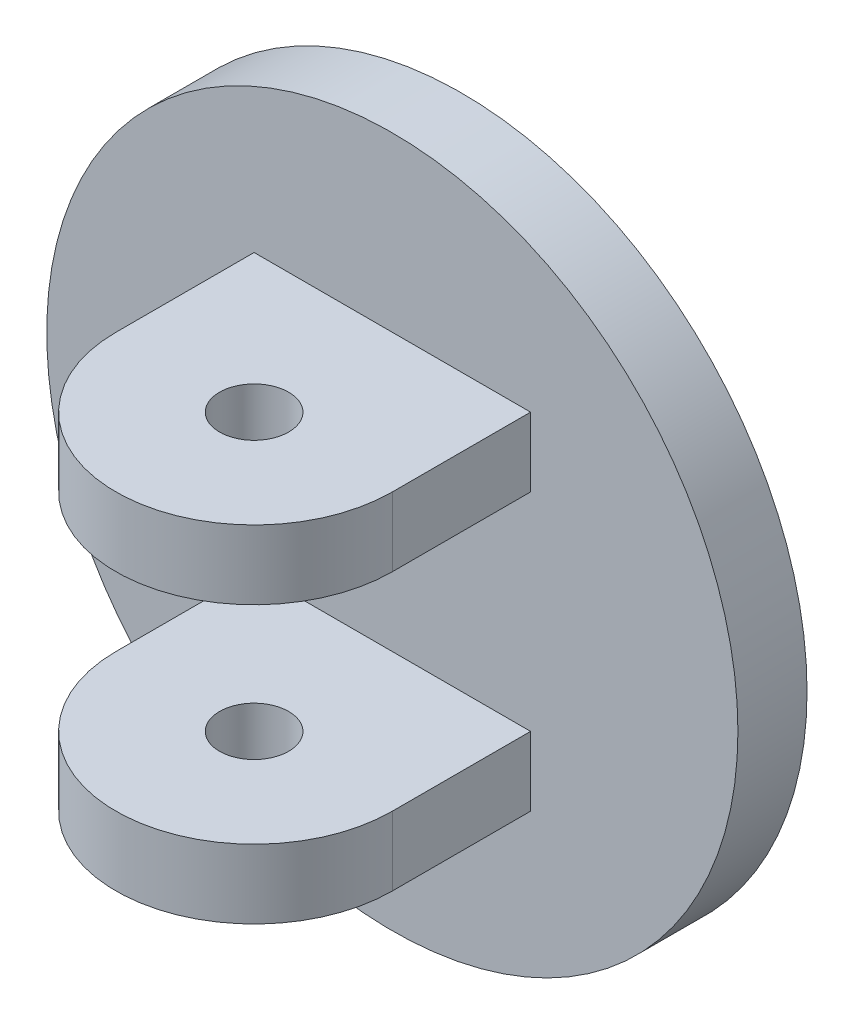
SolidWorks part; units mm, degrees
ref_plane "Front Plane" through (0, 0, 0) normal (0, 0, 1) x (1, 0, 0)
ref_plane "Top Plane" through (0, 0, 0) normal (0, 1, 0) x (1, 0, 0)
ref_plane "Right Plane" through (0, 0, 0) normal (1, 0, 0) x (0, 0, -1)
sketch "Sketch1" plane through (0, 0, 0) normal (0, 0, 1) x (1, 0, 0)
  circle A0 centre (0, 0) radius 50
  dimension "D1" = 100
extrude "Boss-Extrude1" add sketch "Sketch1" along normal blind 10
sketch "Sketch2" plane through (0, 0, 10) normal (0, 0, 1) x (1, 0, 0)
  line L2 (0, 15) -> (20, 15)
  line L4 (0, 25) -> (20, 25)
  line L5 (20, 15) -> (20, 25)
  line L6 (0, 15) -> (-20, 15)
  line L8 (0, 25) -> (-20, 25)
  line L9 (-20, 15) -> (-20, 25)
  line L10 (0, -15) -> (20, -15)
  line L12 (0, -25) -> (20, -25)
  line L13 (20, -15) -> (20, -25)
  line L14 (0, -15) -> (-20, -15)
  line L16 (0, -25) -> (-20, -25)
  line L17 (-20, -15) -> (-20, -25)
  point P4 (0, 0)
  dimension "D1" = 30
  dimension "D2" = 20
  dimension "D3" = 20
  dimension "D4" = 10
  dimension "D5" = 20
  dimension "D6" = 20
  dimension "D7" = 10
extrude "Boss-Extrude2" add sketch "Sketch2" along normal blind 40
sketch "Sketch3" plane through (0, 25, 0) normal (0, 1, 0) x (1, 0, 0)
  circle A0 centre (0, -30) radius 5
  dimension "D1" = 10
extrude "Cut-Extrude1" cut sketch "Sketch3" against normal blind 51 and the other way blind 10
sketch "Sketch4" plane through (0, -25, 0) normal (0, -1, 0) x (1, 0, 0)
  line L0 (20, 50) -> (20, 10) construction
  line L1 (-20, 50) -> (-20, 10) construction
  line L2 (-20, 30) -> (-47.3665, 30)
  line L3 (-47.3665, 30) -> (-38.9642, 74.7454)
  line L4 (-38.9642, 74.7454) -> (40.8393, 70.5722)
  line L5 (40.8393, 70.5722) -> (55.137, 30)
  line L6 (55.137, 30) -> (20, 30)
  arc A0 (20, 30) -> (-20, 30) centre (0, 30) ccw
extrude "Cut-Extrude3" cut sketch "Sketch4" against normal blind 51 and the other way blind 51
